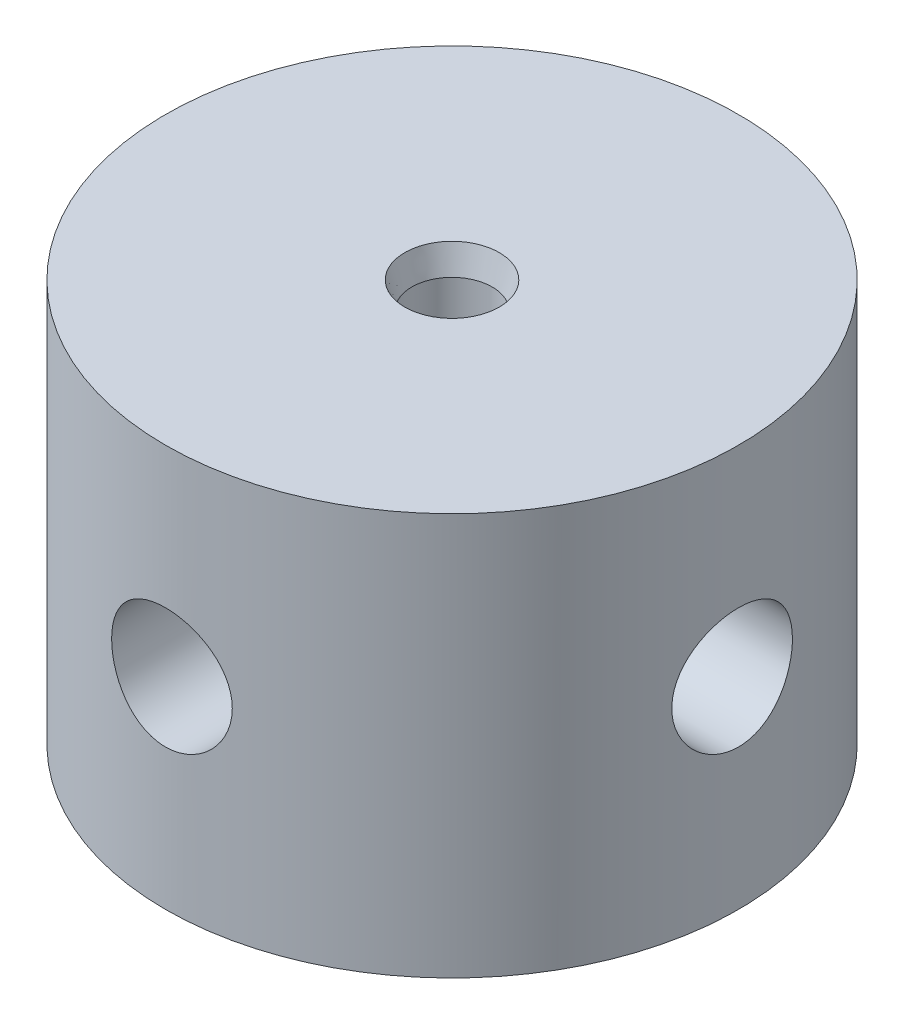
SolidWorks part; units mm, degrees
ref_plane "Front Plane" through (0, 0, 0) normal (0, 0, 1) x (1, 0, 0)
ref_plane "Top Plane" through (0, 0, 0) normal (0, 1, 0) x (1, 0, 0)
ref_plane "Right Plane" through (0, 0, 0) normal (1, 0, 0) x (0, 0, -1)
sketch "Sketch1" plane through (0, 0, 0) normal (0, 0, 1) x (1, 0, 0)
  line L0 (0, 20.7983) -> (0, -18.4168) construction
  line L1 (-12.7012, 0) -> (16.591, 0) construction
  line L2 (-2, 21.9024) -> (-2, -16.8364) construction
  line L3 (-2, 7.7057) -> (-2, -7.7057)
  line L4 (-2, -7.7057) -> (-14.25, -10.9881)
  line L5 (-14.25, 23.0926) -> (-14.25, -16.1225) construction
  line L6 (-2, 7.7057) -> (-2.35, 9.0119)
  line L7 (-2.35, 9.0119) -> (-14.25, 9.0119)
  line L8 (-14.25, 9.0119) -> (-14.25, -10.9881)
  point P10 (-2, 0)
  dimension "D1" = 20
  dimension "D2" = 14.25
  dimension "D3" = 15
  dimension "D4" = 2
  dimension "D5" = 2.35
  dimension "D6" = 75
revolve "Revolve1" add sketch "Sketch1" angle 360 about L0
ref_plane "Plane1" through (14.25, 0, 0) normal (1, 0, 0) x (0, 0, -1)
ref_axis "Axis1" through (0, -10.9881, 0) along (0, 1, 0)
sketch "Sketch2" plane through (14.25, 0, 0) normal (1, 0, 0) x (0, 0, -1)
  line L0 (0, -10.9881) -> (0, 9.0119) construction
  line L2 (2.35, 9.0119) -> (-2.35, 9.0119) construction
  circle A0 centre (0, -0.9881) radius 3
  dimension "D2" = 6
  dimension "D1" = 10
extrude "Cut-Extrude1" cut sketch "Sketch2" against normal blind 9
pattern_circular "CirPattern1" count 4 over 360 about axis through (0, -10.9881, 0) along (0, 1, 0) of "Cut-Extrude1"
